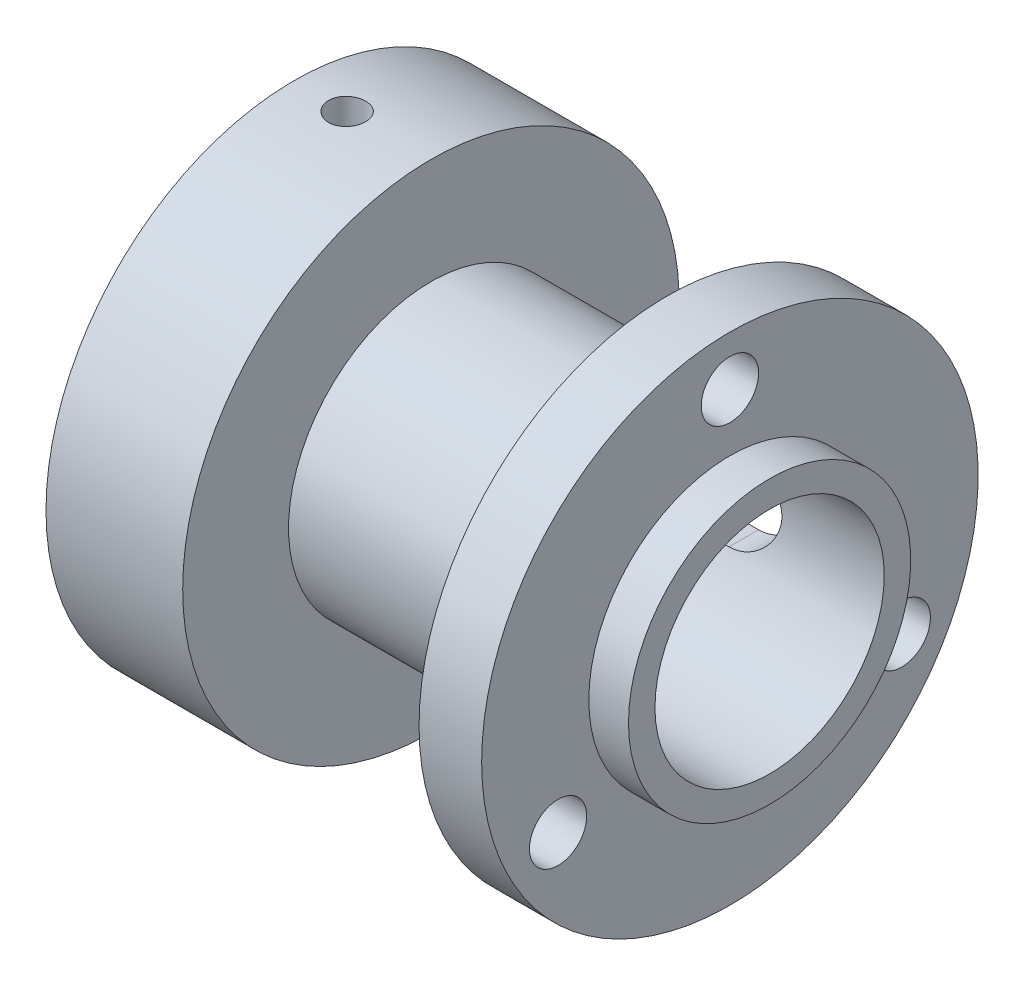
SolidWorks part; units mm, degrees
material "1.0037 (S235JR)"
ref_plane "Front Plane" through (0, 0, 0) normal (0, 0, 1) x (1, 0, 0)
ref_plane "Top Plane" through (0, 0, 0) normal (0, 1, 0) x (1, 0, 0)
ref_plane "Right Plane" through (0, 0, 0) normal (1, 0, 0) x (0, 0, -1)
sketch "Sketch1" plane through (0, 0, 0) normal (0, 0, 1) x (1, 0, 0)
  line L0 (-42.3, 0) -> (68.3954, 0) construction
  line L1 (-42.3, 0) -> (-42.3, 28.15)
  line L2 (-42.3, 28.15) -> (-26.8, 28.15)
  line L3 (-26.8, 28.15) -> (-26.8, 16.15)
  line L4 (-26.8, 16.15) -> (0, 16.15)
  line L5 (0, 16.15) -> (0, 28.15)
  line L6 (0, 28.15) -> (7.1, 28.15)
  line L7 (7.1, 28.15) -> (7.1, 16)
  line L8 (7.1, 16) -> (11.6, 16)
  line L9 (11.6, 16) -> (11.6, 0)
  line L10 (11.6, 13) -> (-32.3, 13)
  line L11 (-32.3, 13) -> (-32.3, 18.15)
  line L12 (-32.3, 18.15) -> (-42.3, 18.15)
  dimension "D1" = 56.3
  dimension "D2" = 32.3
  dimension "D3" = 32
  dimension "D4" = 4.5
  dimension "D5" = 7.1
  dimension "D6" = 26.8
  dimension "D7" = 15.5
  dimension "D8" = 10
  dimension "D9" = 10
  dimension "D10" = 3
revolve "Revolve1" add sketch "Sketch1" angle 360 about L0 region at (-41.7401, 23.15, 0)
ref_plane "Plane1" through (0, 0, -16.15) normal (0, 0, -1) x (-1, 0, 0)
sketch "Sketch2" plane through (0, 0, -16.15) normal (0, 0, -1) x (-1, 0, 0)
  line L0 (21.8, 0) -> (5, 0) construction
  line L1 (21.8, -5) -> (5, -5)
  line L2 (21.8, 5) -> (5, 5)
  line L3 (0, 0) -> (26.8, 0) construction
  line L4 (26.8, 16.15) -> (26.8, -16.15) construction
  line L5 (0, -16.15) -> (0, 16.15) construction
  arc A0 (21.8, -5) -> (21.8, 5) centre (21.8, 0) ccw
  arc A1 (5, 5) -> (5, -5) centre (5, 0) ccw
  point P2 (13.4, 0)
  dimension "D1" = 10
extrude "Cut-Extrude1" cut sketch "Sketch2" against normal up to next
sketch "Sketch3" plane through (7.1, 0, 0) normal (1, 0, 0) x (0, 0, -1)
  line L0 (0, 22.5) -> (0, 0) construction
  circle A0 centre (0, 22.5) radius 3.25
  dimension "D1" = 6.5
  dimension "D2" = 22.5
extrude "Cut-Extrude2" cut sketch "Sketch3" against normal up to next
pattern_circular "CirPattern1" count 3 over 360 about axis through (-42.3, 0, 0) along (-1, 0, 0) of "Cut-Extrude2"
ref_plane "Plane2" through (0, 28.15, 0) normal (0, 1, 0) x (1, 0, 0)
sketch "Sketch4" plane through (0, 28.15, 0) normal (0, 1, 0) x (1, 0, 0)
  line L0 (-42.3, 0) -> (-36.3, 0) construction
  line L1 (-42.3, 28.15) -> (-42.3, -28.15) construction
  dimension "D1" = 6
hole_wizard "M5 Tapped Hole1" positions "3DSketch3" profile "Sketch5" tap size "M5" standard "ISO" end condition up to next
sketch3d "3DSketch3"
  point P0 (-36.3, 28.15, 0)
  point P3 (-36.3, 28.15, 0)
  point P6 (-36.3, 28.15, 0)
sketch "Sketch5" plane through (-36.3, 28.15, 0) normal (1, 0, 0) x (0, 0, 1)
  line L0 (0, 0) -> (0, 28.15)
  line L1 (0, 28.15) -> (2.1, 28.15)
  line L2 (2.1, 28.15) -> (2.1, 0)
  line L5 (2.1, 0) -> (0, 0)
  line L11 (0, -6.35) -> (0, 107.95) construction
  dimension "Thru Tap Drill Dia." = 4.2
  dimension "Thru Tap Drill Depth" = 28.15
cosmetic thread "Hole Thread3" parameters "D2"=5
